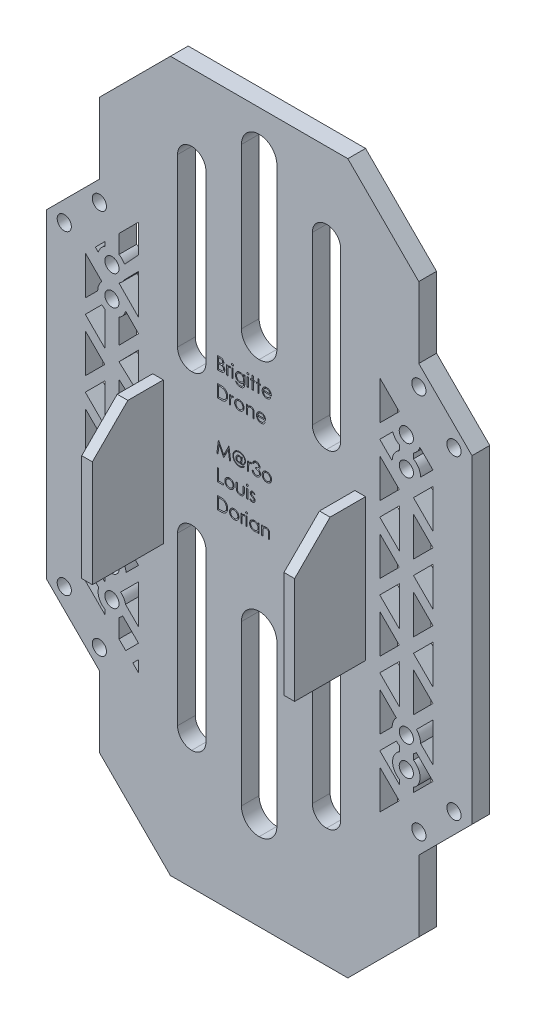
SolidWorks part; units mm, degrees
ref_plane "Plan de face" through (0, 0, 0) normal (0, 0, 1) x (1, 0, 0)
ref_plane "Plan de dessus" through (0, 0, 0) normal (0, 1, 0) x (1, 0, 0)
ref_plane "Plan de droite" through (0, 0, 0) normal (1, 0, 0) x (0, 0, -1)
sketch "Esquisse1" plane through (0, 0, 0) normal (0, 0, 1) x (1, 0, 0)
  line L0 (-41.0719, 30.2056) -> (78.9281, 30.2056)
  line L1 (78.9281, 30.2056) -> (78.9281, -89.7944)
  line L2 (78.9281, -89.7944) -> (-41.0719, -89.7944)
  line L3 (-41.0719, -89.7944) -> (-41.0719, 30.2056)
  dimension "D1" = 120
  dimension "D2" = 120
extrude "Boss.-Extru.2" add sketch "Esquisse1" along normal blind 5
sketch "Esquisse3" plane through (0, 0, 0) normal (0, 0, -1) x (-1, 0, 0)
sketch "Esquisse7" plane through (0, 0, 5) normal (0, 0, 1) x (1, 0, 0)
sketch "Esquisse9" plane through (0, 0, 5) normal (0, 0, 1) x (1, 0, 0)
  line L0 (-41.0719, -89.7944) -> (78.9281, -89.7944) construction
  line L1 (78.9281, -89.7944) -> (78.9281, 30.2056) construction
  circle A0 centre (-22.5719, -62.2944) radius 2
  circle A1 centre (-22.5719, 2.7056) radius 2
  circle A2 centre (60.4281, 2.7056) radius 2
  circle A3 centre (60.4281, -62.2944) radius 2
  dimension "D5" = 4
  dimension "D6" = 4
  dimension "D7" = 4
  dimension "D8" = 4
  dimension "D1" = 83
  dimension "D2" = 83
  dimension "D3" = 18.5
  dimension "D4" = 65
  dimension "D9" = 27.5
  dimension "D10" = 27.5
  dimension "D11" = 18.5
  dimension "D12" = 65
chamfer "Chanfrein5" distance 15 angle 45 1 edges at (78.9281, -89.7944, 2.5)
chamfer "Chanfrein6" distance 15 angle 45 1 edges at (78.9281, 30.2056, 2.5)
chamfer "Chanfrein7" distance 15 angle 45 1 edges at (-41.0719, 30.2056, 2.5)
chamfer "Chanfrein8" distance 15 angle 45 1 edges at (-41.0719, -89.7944, 2.5)
sketch "Esquisse21" plane through (0, -89.7944, 0) normal (0, -1, 0) x (-1, 0, 0)
  line L0 (26.0719, -5) -> (26.0719, 0)
  line L1 (26.0719, 0) -> (-63.9281, 0)
  line L2 (-63.9281, 0) -> (-63.9281, -5)
  line L3 (-63.9281, -5) -> (26.0719, -5)
extrude "Boss.-Extru.7" add sketch "Esquisse21" along normal blind 40
sketch "Esquisse22" plane through (0, 30.2056, 0) normal (0, 1, 0) x (1, 0, 0)
  line L0 (63.9281, -5) -> (63.9281, 0)
  line L1 (63.9281, 0) -> (-26.0719, 0) construction
  line L2 (63.9281, 0) -> (-26.0719, 0)
  line L3 (-26.0719, 0) -> (-26.0719, -5)
  line L4 (-26.0719, -5) -> (63.9281, -5)
extrude "Boss.-Extru.8" add sketch "Esquisse22" along normal blind 40
chamfer "Chanfrein23" distance 20 angle 45 4 edges at (-26.0719, -129.7944, 2.5) (63.9281, -129.7944, 2.5) (-26.0719, 70.2056, 2.5) (63.9281, 70.2056, 2.5)
sketch "Esquisse23" plane through (0, 0, 5) normal (0, 0, 1) x (1, 0, 0)
  line L0 (-41.0719, -74.7944) -> (-26.0719, -89.7944) construction
  line L2 (-35.9963, -74.2132) -> (-26.0968, -84.1127)
  line L3 (78.9281, 15.2056) -> (63.9281, 30.2056) construction
  line L4 (-35.9963, -74.2132) -> (-31.0465, -79.1629)
  line L5 (63.9281, -89.7944) -> (78.9281, -74.7944) construction
  line L6 (-31.0465, -79.1629) -> (-22.5612, -70.6777)
  line L9 (63.9532, -84.1124) -> (73.8527, -74.2129)
  line L10 (63.9532, -84.1124) -> (68.903, -79.1626)
  line L11 (68.903, -79.1626) -> (60.4177, -70.6774)
  line L14 (63.9532, 24.5237) -> (73.8527, 14.6242)
  line L15 (73.8527, 14.6242) -> (68.9029, 19.5739)
  line L16 (68.9029, 19.5739) -> (60.4176, 11.0886)
  line L17 (-35.9969, 14.6238) -> (-26.0974, 24.5232)
  line L18 (-26.0974, 24.5232) -> (-31.0472, 19.5735)
  line L19 (-31.0472, 19.5735) -> (-22.5619, 11.0882)
  line L27 (-26.0719, 30.2056) -> (-41.0719, 15.2056) construction
  line L31 (-41.0719, 15.2056) -> (-41.0719, -74.7944) construction
  circle A0 centre (-35.9963, -74.2132) radius 2
  circle A1 centre (-26.0968, -84.1127) radius 2
  circle A2 centre (-26.0974, 24.5232) radius 2
  circle A3 centre (-35.9969, 14.6238) radius 2
  circle A4 centre (63.9532, 24.5237) radius 2
  circle A5 centre (73.8527, 14.6242) radius 2
  circle A6 centre (63.9532, -84.1124) radius 2
  circle A7 centre (73.8527, -74.2129) radius 2
  circle A8 centre (-22.5612, -70.6777) radius 2
  circle A9 centre (60.4177, -70.6774) radius 2
  circle A10 centre (60.4176, 11.0886) radius 2
  circle A11 centre (-22.5619, 11.0882) radius 2
  dimension "D3" = 4
  dimension "D4" = 4
  dimension "D6" = 4
  dimension "D7" = 4
  dimension "D10" = 5.6818
  dimension "D15" = 4
  dimension "D16" = 4
  dimension "D19" = 14
  dimension "D23" = 4
  dimension "D24" = 4
  dimension "D26" = 4
  dimension "D27" = 4
  dimension "D28" = 4
  dimension "D30" = 4
  dimension "D1" = 4
  dimension "D2" = 4
  dimension "D5" = 14
  dimension "D8" = 14
  dimension "D9" = 4
  dimension "D11" = 4
  dimension "D12" = 5.075
  dimension "D13" = 14
  dimension "D14" = 4
  dimension "D17" = 4
  dimension "D18" = 5.682
  dimension "D20" = 4
  dimension "D21" = 5.682
  dimension "D22" = 4
  dimension "D25" = 12
  dimension "D29" = 12
  dimension "D31" = 12
  dimension "D32" = 12
extrude "Enlèv. mat.-Extru.1" cut sketch "Esquisse23" against normal blind 10 contours A0 | A1 | A6 | A7 | A5 | A4 | A10 | A11 | A2 | A3 | A8 | A9
sketch "Esquisse24" plane through (0, 0, 5) normal (0, 0, 1) x (1, 0, 0)
  line L0 (63.9281, -89.7944) -> (78.9281, -74.7944) construction
  circle A0 centre (63.5389, -84.5268) radius 2.5407
  circle A1 centre (73.4383, -74.6273) radius 2.5147
  dimension "D1" = 4
  dimension "D2" = 4
  dimension "D3" = 14
  dimension "D4" = 5.282
sketch "Sketch1" plane through (0, 0, 5) normal (0, 0, 1) x (1, 0, 0)
  line L1 (13.9281, -107.7944) -> (23.9281, -107.7944)
  line L2 (13.9281, -107.7944) -> (13.9281, -52.7944)
  line L3 (13.9281, -52.7944) -> (23.9281, -52.7944)
  line L4 (23.9281, -107.7944) -> (23.9281, -52.7944)
  line L6 (43.9281, -129.7944) -> (-6.0719, -129.7944) construction
  dimension "D1" = 10
  dimension "D2" = 55
  dimension "D3" = 40
  dimension "D4" = 22
extrude "Cut-Extrude2" cut sketch "Sketch1" against normal blind 5 contours L2 L1 L4 L3
fillet "Fillet2" radius 5 1 edges at (13.9281, -107.7944, 2.5)
fillet "Fillet3" radius 5 3 edges at (13.9281, -52.7944, 2.5) (23.9281, -52.7944, 2.5) (23.9281, -107.7944, 2.5)
sketch "Sketch2" plane through (0, 0, 5) normal (0, 0, 1) x (1, 0, 0)
  line L0 (23.9281, -102.7944) -> (23.9281, -57.7944) construction
  line L1 (41.9281, -96.2103) -> (33.9281, -96.2103)
  line L2 (41.9281, -96.2103) -> (41.9281, -41.2103)
  line L3 (41.9281, -41.2103) -> (33.9281, -41.2103)
  line L4 (33.9281, -96.2103) -> (33.9281, -41.2103)
  line L5 (13.9281, -102.7944) -> (13.9281, -57.7944) construction
  line L6 (3.9281, -96.2103) -> (-4.0719, -96.2103)
  line L7 (3.9281, -96.2103) -> (3.9281, -41.2103)
  line L8 (3.9281, -41.2103) -> (-4.0719, -41.2103)
  line L9 (-4.0719, -96.2103) -> (-4.0719, -41.2103)
  dimension "D1" = 10
  dimension "D2" = 10
  dimension "D3" = 8
  dimension "D4" = 8
  dimension "D5" = 55
  dimension "D6" = 55
sketch "Sketch3" plane through (0, 0, 5) normal (0, 0, 1) x (1, 0, 0)
  line L0 (78.9281, -74.7944) -> (78.9281, 15.2056) construction
  line L1 (23.9281, 63.6661) -> (13.9281, 63.6661)
  line L2 (23.9281, 63.6661) -> (23.9281, 8.6661)
  line L3 (23.9281, 8.6661) -> (13.9281, 8.6661)
  line L4 (13.9281, 63.6661) -> (13.9281, 8.6661)
  dimension "D1" = 10
  dimension "D2" = 55
  dimension "D3" = 55
extrude "Cut-Extrude4" cut sketch "Sketch3" against normal blind 5
fillet "Fillet11" radius 5 4 edges at (13.9281, 63.6661, 2.5) (23.9281, 63.6661, 2.5) (23.9281, 8.6661, 2.5) (13.9281, 8.6661, 2.5)
extrude "Cut-Extrude5" cut sketch "Sketch2" against normal blind 8
sketch "Sketch4" plane through (0, 0, 5) normal (0, 0, 1) x (1, 0, 0)
  line L0 (13.9281, 58.6661) -> (13.9281, 13.6661) construction
  line L1 (-4.0719, 51.2056) -> (3.9281, 51.2056)
  line L2 (-4.0719, 51.2056) -> (-4.0719, -3.7944)
  line L3 (-4.0719, -3.7944) -> (3.9281, -3.7944)
  line L4 (3.9281, 51.2056) -> (3.9281, -3.7944)
  line L5 (33.9281, 51.2056) -> (41.9281, 51.2056)
  line L6 (33.9281, 51.2056) -> (33.9281, -3.7944)
  line L7 (33.9281, -3.7944) -> (41.9281, -3.7944)
  line L8 (41.9281, 51.2056) -> (41.9281, -3.7944)
  line L9 (23.9281, 13.6661) -> (23.9281, 58.6661) construction
  line L10 (-6.0719, 70.2056) -> (43.9281, 70.2056) construction
  dimension "D1" = 8
  dimension "D2" = 55
  dimension "D3" = 55
  dimension "D4" = 8
  dimension "D5" = 10
  dimension "D6" = 10
  dimension "D7" = 19
  dimension "D8" = 19
extrude "Cut-Extrude6" cut sketch "Sketch4" against normal blind 8
fillet "Fillet12" radius 4 4 edges at (33.9281, 51.2056, 2.5) (41.9281, 51.2056, 2.5) (41.9281, -3.7944, 2.5) (33.9281, -3.7944, 2.5)
fillet "Fillet13" radius 4 4 edges at (-4.0719, -3.7944, 2.5) (3.9281, -3.7944, 2.5) (-4.0719, 51.2056, 2.5) (3.9281, 51.2056, 2.5)
fillet "Fillet14" radius 4 4 edges at (3.9281, -41.2103, 2.5) (-4.0719, -41.2103, 2.5) (-4.0719, -96.2103, 2.5) (3.9281, -96.2103, 2.5)
fillet "Fillet15" radius 4 4 edges at (41.9281, -96.2103, 2.5) (33.9281, -96.2103, 2.5) (33.9281, -41.2103, 2.5) (41.9281, -41.2103, 2.5)
sketch "Sketch5" plane through (0, 0, 5) normal (0, 0, 1) x (1, 0, 0)
  line L0 (-6.0719, 70.2056) -> (43.9281, 70.2056) construction
  line L1 (-11.0719, -9.7944) -> (-8.0719, -9.7944)
  line L2 (-11.0719, -9.7944) -> (-11.0719, -49.7944)
  line L3 (-11.0719, -49.7944) -> (-8.0719, -49.7944)
  line L4 (-8.0719, -9.7944) -> (-8.0719, -49.7944)
  line L5 (45.9281, -9.7944) -> (48.9281, -9.7944)
  line L6 (45.9281, -9.7944) -> (45.9281, -49.7944)
  line L7 (45.9281, -49.7944) -> (48.9281, -49.7944)
  line L8 (48.9281, -9.7944) -> (48.9281, -49.7944)
  line L9 (-41.0719, 15.2056) -> (-41.0719, -74.7944) construction
  dimension "D1" = 40
  dimension "D2" = 40
  dimension "D3" = 80
  dimension "D4" = 80
  dimension "D5" = 3
  dimension "D6" = 3
  dimension "D7" = 54
  dimension "D8" = 30
extrude "Boss-Extrude1" add sketch "Sketch5" along normal blind 20
chamfer "Chamfer1" distance 10 angle 45 1 edges at (47.4281, -9.7944, 25)
chamfer "Chamfer2" distance 10 angle 45 1 edges at (-9.5719, -9.7944, 25)
extrude "Cut-Extrude7" cut sketch "Esquisse9" against normal blind 10
sketch "Sketch6" plane through (0, 0, 5) normal (0, 0, 1) x (1, 0, 0)
  line L0 (-15.0719, -120.7944) -> (-15.0719, 61.2056)
  line L1 (-26.0719, -109.7944) -> (-6.0719, -129.7944) construction
  line L2 (-6.0719, 70.2056) -> (-26.0719, 50.2056) construction
  line L3 (-30.0719, -85.7944) -> (-30.0719, 26.2056)
  line L4 (-41.0719, -74.7944) -> (-26.0719, -89.7944) construction
  line L5 (-26.0719, 30.2056) -> (-41.0719, 15.2056) construction
  line L6 (-41.0719, 15.2056) -> (-41.0719, -74.7944) construction
  line L7 (-15.0719, 17.2056) -> (-20.5719, 11.2719)
  line L8 (-20.5719, -115.2944) -> (-20.5719, 55.7056)
  line L9 (-24.5719, -53.8095) -> (-24.5719, 126.1905)
  line L10 (-24.5719, -53.8095) -> (-24.5719, -111.2944)
  line L11 (-15.0719, -84.7944) -> (-30.0719, -69.7944)
  line L12 (-15.0719, 25.2056) -> (-30.0719, 10.2056)
  line L13 (-15.0719, 13.2056) -> (-20.5719, 7.5964)
  line L14 (-20.5719, 7.5964) -> (-15.0719, 1.9874)
  line L15 (-20.5719, 7.5964) -> (-15.0719, 7.5964)
  line L16 (-15.0719, -6.0126) -> (-20.5719, -11.6216)
  line L17 (-20.5719, 3.5964) -> (-20.2132, 3.2306)
  line L18 (-19.2957, 2.2949) -> (-15.0719, -2.0126)
  line L19 (-15.0719, -2.0126) -> (-20.5719, -7.6216)
  line L20 (-20.5719, -11.6216) -> (-15.0719, -16.6452)
  line L21 (-20.5719, -15.9374) -> (-15.0719, -20.6452)
  line L22 (-15.0719, -20.6452) -> (-20.5719, -26.0772)
  line L23 (-15.0719, -24.6452) -> (-20.5719, -30.0772)
  line L24 (-20.5719, -30.0772) -> (-15.0719, -35.5772)
  line L25 (-20.5719, -34.0772) -> (-15.0719, -39.5772)
  line L26 (-15.0719, -39.5772) -> (-20.5719, -45.0772)
  line L27 (-20.5719, -49.0772) -> (-15.0719, -43.5772)
  line L28 (-20.5719, -49.0772) -> (-15.0719, -54.5772)
  line L29 (-20.5719, -53.0772) -> (-15.0719, -58.5772)
  line L30 (-15.0719, -58.5772) -> (-20.5719, -58.5772)
  line L31 (-15.0719, -58.5772) -> (-20.5719, -64.0772)
  line L32 (-20.5719, -68.0772) -> (-15.0719, -68.0772)
  line L36 (-20.5719, -68.0772) -> (-15.0719, -73.5772)
  line L37 (-15.0719, -77.5772) -> (-20.5719, -77.5772)
  line L38 (-15.0719, -77.5772) -> (-20.5719, -83.0772)
  line L39 (-30.0719, 10.2056) -> (-24.5719, 4.7056)
  line L40 (-27.2435, 13.034) -> (-24.5719, 10.3625)
  line L41 (-24.5719, 4.7056) -> (-30.0719, 4.7056)
  line L43 (-24.5719, 4.7056) -> (-30.0719, -0.7944)
  line L45 (-30.0719, -65.7988) -> (-30.0719, -69.7944)
  line L46 (-30.0719, -4.7944) -> (-24.5719, -4.7944)
  line L47 (-30.0719, -4.7944) -> (-24.5719, -10.2944)
  line L48 (-30.0719, -8.7944) -> (-24.5719, -14.2944)
  line L49 (-24.5719, -14.2944) -> (-30.0719, -14.2944)
  line L50 (-24.5719, -14.2944) -> (-30.0719, -19.7944)
  line L51 (-24.5719, -18.2944) -> (-30.0719, -23.7944)
  line L52 (-30.0719, -23.7944) -> (-24.5719, -23.7944)
  line L53 (-30.0719, -23.7944) -> (-24.5719, -29.2944)
  line L54 (-30.0719, -27.7944) -> (-24.5719, -33.2944)
  line L55 (-24.5719, -33.2944) -> (-30.0719, -33.2944)
  line L56 (-24.5719, -33.2944) -> (-30.0719, -38.9521)
  line L57 (-24.5719, -37.2944) -> (-30.0719, -42.9521)
  line L58 (-30.0719, -42.9521) -> (-24.5719, -42.9521)
  line L59 (-30.0719, -42.9521) -> (-24.5719, -48.2988)
  line L60 (-30.0719, -46.9521) -> (-24.5719, -52.2988)
  line L61 (-24.5719, -52.2988) -> (-30.0719, -52.2988)
  line L62 (-24.5719, -52.2988) -> (-30.0719, -57.7988)
  line L63 (-24.5719, -56.2988) -> (-30.0719, -61.7988)
  line L64 (-30.0719, -61.7988) -> (-24.5719, -61.7988)
  line L66 (-30.0719, -65.7988) -> (-24.5719, -71.2988)
  line L67 (-30.0719, -4.7944) -> (-24.5719, 0.7056)
  line L68 (-24.5719, -75.2988) -> (-24.5697, -75.2966)
  line L70 (-30.0719, -69.7944) -> (-26.5697, -73.2966)
  line L71 (-20.5719, -68.0772) -> (-15.0719, -62.5772)
  line L72 (-20.5719, -72.0772) -> (-15.0719, -77.5772)
  line L73 (-15.0719, -81.5772) -> (-16.6805, -83.1858)
  line L74 (-30.0719, -61.7988) -> (-24.5719, -67.3403)
  circle A0 centre (-22.5719, -62.2944) radius 4
  circle A2 centre (-22.5612, -70.6777) radius 3.8963
  circle A3 centre (-22.5619, 11.0882) radius 4
  circle A4 centre (-22.5719, 2.7056) radius 4
  point P105 (0, 0)
  point P116 (0, 0)
  point P117 (-25.8481, -3.0448)
  dimension "D6" = 8
  dimension "D32" = 8
  dimension "D56" = 8
  dimension "D1" = 15
  dimension "D2" = 11
  dimension "D3" = 8
  dimension "D4" = 4
  dimension "D7" = 4
  dimension "D8" = 36
  dimension "D9" = 16
  dimension "D10" = 36
  dimension "D11" = 16
  dimension "D12" = 4
  dimension "D13" = 4
  dimension "D14" = 4
  dimension "D15" = 4
  dimension "D16" = 4
  dimension "D17" = 4
  dimension "D18" = 4
  dimension "D19" = 4
  dimension "D20" = 4
  dimension "D21" = 4
  dimension "D22" = 4
  dimension "D23" = 4
  dimension "D24" = 5.5
  dimension "D25" = 4
  dimension "D26" = 4
  dimension "D27" = 4
  dimension "D28" = 4
  dimension "D29" = 9.5
  dimension "D30" = 4
  dimension "D31" = 0
  dimension "D33" = 4
  dimension "D34" = 5.5
  dimension "D35" = 4
  dimension "D36" = 5.5
  dimension "D37" = 4
  dimension "D38" = 4
  dimension "D39" = 5.5
  dimension "D40" = 4
  dimension "D41" = 4
  dimension "D42" = 4
  dimension "D43" = 4
  dimension "D44" = 4
  dimension "D45" = 4
  dimension "D46" = 4
  dimension "D47" = 4
  dimension "D48" = 4
  dimension "D49" = 4
  dimension "D50" = 4
  dimension "D51" = 4
  dimension "D52" = 5.5
  dimension "D53" = 5.5
  dimension "D54" = 11
  dimension "D57" = 4
  dimension "D58" = 4
  dimension "D59" = 5.5
extrude "Cut-Extrude8" cut sketch "Sketch6" against normal blind 10 contours L0 L73 L11 | L38 L37 L8 L11 | A2 L8 L37 L72 | A2 L36 L0 L32 | A2 L32 L0 L71 | A0 L31 L30 L8 | L30 L29 L8 | L27 L28 L0 | L26 L25 L8 | L23 L24 L0 | L22 L21 L8 | L16 L20 L0 | A4 L8 L19 L18 | L15 L14 L0 | A3 L13 L15 L0 | A3 L7 L0 L12 L8 | A3 L9 L12 L40 | A4 L39 L3 L41 | A4 L41 L3 L43 | A4 L67 L46 L9 | L46 L47 L9 | L49 L48 L3 | L50 L49 L3 | L51 L52 L9 | L52 L53 L9 | L55 L54 L3 | L56 L55 L3 | L57 L58 L9 | L58 L59 L9 | L61 L60 L3 | L62 L61 L3 | A0 L10 L63 L64 | A0 L64 L74 L10 | A2 L66 L3 L11 L10 region at (-15.6081, -83.1858, 5) region at (-18.366, -78.8605, 5) region at (-18.6256, -75.9461, 5) region at (-16.7125, -69.9954, 5) region at (-16.8606, -66.2204, 5) region at (-27.868, -70.1846, 5) region at (-18.7386, -56.7438, 5) region at (-17.9347, -59.6603, 5) region at (-16.9053, -49.0772, 5) region at (-27.0269, -63.812, 5) region at (-26.776, -59.7222, 5) region at (-18.7386, -39.5772, 5) region at (-28.2386, -54.1321, 5) region at (-16.9053, -30.0999, 5) region at (-28.2386, -50.5165, 5) region at (-26.4053, -44.7343, 5) region at (-18.7386, -20.8866, 5) region at (-26.4053, -41.0662, 5) region at (-16.9053, -11.4265, 5) region at (-28.2386, -35.1803, 5) region at (-28.2386, -31.4611, 5) region at (-18.5306, -2.6196, 5) region at (-26.4053, -25.6277, 5) region at (-16.9053, 5.7267, 5) region at (-26.4053, -21.9611, 5) region at (-16.8706, 9.4797, 5) region at (-26.4727, -3.0866, 5) region at (-28.2386, -16.1277, 5) region at (-26.4053, -6.6277, 5) region at (-28.2386, -12.4611, 5) region at (-17.7026, 18.6721, 5) region at (-28.538, 2.7336, 5) region at (-28.3642, 6.6064, 5) region at (-25.8309, 13.8848, 5)
sketch "Sketch9" plane through (0, 0, 5) normal (0, 0, 1) x (1, 0, 0)
  line L0 (78.9281, -74.7944) -> (78.9281, 15.2056) construction
  line L1 (58.4281, -60.2944) -> (52.9281, -60.2944)
  line L2 (43.9281, -129.7944) -> (63.9281, -109.7944) construction
  line L3 (62.4281, -111.2944) -> (62.4281, 51.7056)
  line L4 (63.9281, 50.2056) -> (43.9281, 70.2056) construction
  line L5 (58.4281, -115.2944) -> (58.4281, 55.7056)
  line L6 (67.9281, -85.7944) -> (67.9281, 26.2056)
  line L7 (63.9281, -89.7944) -> (78.9281, -74.7944) construction
  line L8 (78.9281, 15.2056) -> (63.9281, 30.2056) construction
  line L9 (52.9281, -120.7944) -> (52.9281, 61.2056)
  line L10 (52.9281, -120.7944) -> (52.9281, -84.7944)
  line L11 (67.9281, -85.7944) -> (67.9281, -69.7944)
  line L12 (52.9281, -84.7944) -> (67.9281, -69.7944)
  line L13 (52.9281, -79.2944) -> (58.4281, -79.2944)
  line L14 (58.4281, -79.2944) -> (52.9281, -73.7944)
  line L15 (52.9281, -69.7944) -> (58.4281, -75.2944)
  line L16 (52.9281, -69.7944) -> (58.4281, -69.7944)
  line L17 (52.9281, -69.7944) -> (58.4281, -64.2944)
  line L18 (52.9281, -65.7944) -> (58.4281, -60.2944)
  line L19 (58.4281, -60.2944) -> (52.9281, -54.7944)
  line L20 (52.9281, -50.7944) -> (58.4281, -56.2944)
  line L21 (52.9281, -50.7944) -> (58.4281, -50.7944)
  line L22 (52.9281, -50.7944) -> (58.4281, -45.2944)
  line L23 (52.9281, -46.7944) -> (58.4281, -41.2944)
  line L24 (58.4281, -41.2944) -> (52.9281, -41.2944)
  line L25 (58.4281, -41.2944) -> (52.9281, -35.7944)
  line L26 (52.9281, -31.7944) -> (58.4281, -37.2944)
  line L27 (52.9281, -31.7944) -> (58.4281, -31.7944)
  line L28 (52.9281, -31.7944) -> (58.4281, -26.2944)
  line L29 (52.9281, -27.7944) -> (58.4281, -22.2944)
  line L30 (58.4281, -22.2944) -> (52.9281, -22.2944)
  line L31 (58.4281, -22.2944) -> (52.9281, -16.7944)
  line L32 (52.9281, -12.7944) -> (58.4281, -18.2944)
  line L33 (52.9281, -12.7944) -> (58.4281, -12.7944)
  line L34 (52.9281, -12.7944) -> (58.4281, -7.2944)
  line L35 (52.9281, -8.7944) -> (58.4281, -3.2944)
  line L36 (58.4281, -3.2944) -> (52.9281, -3.2944)
  line L37 (58.4281, -3.2944) -> (52.9281, 2.2056)
  line L38 (58.4281, 0.7056) -> (52.9281, 6.2056)
  line L39 (52.9281, 6.2056) -> (58.4281, 6.2056)
  line L40 (52.9281, 6.2056) -> (58.4281, 11.7056)
  line L41 (52.9281, 10.2056) -> (58.4281, 15.7056)
  line L42 (52.9281, 61.2056) -> (52.9281, 25.2056)
  line L43 (67.9281, 26.2056) -> (67.9281, 10.2056)
  line L44 (52.9281, 25.2056) -> (67.9281, 10.2056)
  line L45 (58.4281, 15.7056) -> (52.9281, 15.7056)
  line L46 (58.4281, 15.7056) -> (52.9281, 21.2056)
  line L47 (58.4281, 19.7056) -> (52.9281, 25.2056)
  line L48 (67.9281, -69.7944) -> (62.4281, -69.7944)
  line L49 (67.9281, -69.7944) -> (62.4281, -64.2944)
  line L50 (67.9281, -65.7944) -> (62.4281, -60.2944)
  line L51 (62.4281, -60.2944) -> (67.9281, -60.2944)
  line L52 (62.4281, -60.2944) -> (67.9281, -54.7944)
  line L53 (62.4281, -56.2944) -> (67.9281, -50.7944)
  line L54 (67.9281, -50.7944) -> (62.4281, -50.7944)
  line L55 (67.9281, -50.7944) -> (62.4281, -45.2944)
  line L56 (62.4281, -41.2944) -> (67.9281, -46.7944)
  line L57 (62.4281, -41.2944) -> (67.9281, -41.2944)
  line L58 (62.4281, -41.2944) -> (67.9281, -35.7944)
  line L59 (62.4281, -37.2944) -> (67.9281, -31.7944)
  line L60 (67.9281, -31.7944) -> (62.4281, -31.7944)
  line L61 (67.9281, -31.7944) -> (62.4281, -26.2944)
  line L62 (67.9281, -27.7944) -> (62.4281, -22.2944)
  line L63 (62.4281, -22.2944) -> (67.9281, -22.2944)
  line L64 (62.4281, -22.2944) -> (67.9281, -16.7944)
  line L65 (62.4281, -18.2944) -> (67.9281, -12.7944)
  line L66 (67.9281, -12.7944) -> (62.4281, -12.7944)
  line L67 (67.9281, -12.7944) -> (62.4281, -7.2944)
  line L68 (67.9281, -8.7944) -> (62.4281, -3.2944)
  line L69 (62.4281, -3.2944) -> (67.9281, -3.2944)
  line L70 (62.4281, -3.2944) -> (67.9281, 2.2056)
  line L71 (62.4281, 0.7056) -> (67.9281, 6.2056)
  line L72 (67.9281, 6.2056) -> (62.4281, 6.2056)
  line L73 (67.9281, 6.2056) -> (62.4281, 11.7056)
  circle A0 centre (60.4281, -62.2944) radius 4
  circle A1 centre (60.4281, 2.7056) radius 4
  circle A2 centre (60.4176, 11.0886) radius 4
  circle A3 centre (60.4177, -70.6774) radius 3.8769
  dimension "D12" = 8
  dimension "D13" = 8
  dimension "D73" = 8
  dimension "D1" = 11
  dimension "D2" = 4
  dimension "D3" = 5.5
  dimension "D4" = 5.5
  dimension "D5" = 36
  dimension "D6" = 16
  dimension "D7" = 5.5
  dimension "D8" = 4
  dimension "D9" = 5.5
  dimension "D10" = 4
  dimension "D11" = 5.5
  dimension "D14" = 4
  dimension "D15" = 4
  dimension "D16" = 5.5
  dimension "D17" = 5.5
  dimension "D18" = 5.5
  dimension "D19" = 4
  dimension "D20" = 4
  dimension "D21" = 5.5
  dimension "D22" = 5.5
  dimension "D23" = 4
  dimension "D24" = 4
  dimension "D25" = 5.5
  dimension "D26" = 5.5
  dimension "D27" = 4
  dimension "D28" = 4
  dimension "D29" = 5.5
  dimension "D30" = 4
  dimension "D31" = 4
  dimension "D32" = 5.5
  dimension "D33" = 4
  dimension "D34" = 4
  dimension "D35" = 5.5
  dimension "D36" = 4
  dimension "D37" = 4
  dimension "D38" = 5.5
  dimension "D39" = 4
  dimension "D40" = 4
  dimension "D41" = 5.5
  dimension "D42" = 4
  dimension "D43" = 4
  dimension "D44" = 36
  dimension "D45" = 5.5
  dimension "D46" = 4
  dimension "D47" = 4
  dimension "D48" = 5.5
  dimension "D49" = 4
  dimension "D50" = 4
  dimension "D51" = 5.5
  dimension "D52" = 4
  dimension "D53" = 4
  dimension "D54" = 5.5
  dimension "D55" = 4
  dimension "D56" = 4
  dimension "D57" = 4
  dimension "D58" = 4
  dimension "D59" = 4
  dimension "D60" = 5.5
  dimension "D61" = 4
  dimension "D62" = 5.5
  dimension "D63" = 4
  dimension "D64" = 4
  dimension "D65" = 5.5
  dimension "D66" = 4
  dimension "D67" = 4
  dimension "D68" = 5.5
  dimension "D69" = 4
  dimension "D70" = 4
  dimension "D71" = 4
  dimension "D72" = 5.5
extrude "Cut-Extrude10" cut sketch "Sketch9" against normal blind 10 contours L13 L14 L9 | L16 L15 L5 | A0 L17 L16 L5 | L9 L18 L1 | L1 L19 L9 | L22 L21 L5 | L21 L20 L5 | L23 L24 L9 | L24 L25 L9 | L27 L26 L5 | L28 L27 L5 | L30 L31 L9 | L29 L30 L9 | L33 L32 L5 | L34 L33 L5 | A1 L37 L9 L36 | L35 L36 L9 | L40 L39 L5 | A1 L5 L39 L38 | L41 L45 L9 | L45 L46 L9 | L13 L9 L12 | L72 L73 L3 | A1 L71 L72 L3 | A1 L70 L69 L6 | L69 L68 L6 | L66 L67 L3 | L65 L66 L3 | L64 L63 L6 | L63 L62 L6 | L60 L61 L3 | L59 L60 L3 | L58 L57 L6 | L57 L56 L6 | L54 L55 L3 | L53 L54 L3 | L52 L51 L6 | L51 L50 L6 | A0 L3 L48 L49 | L12 L48 L3 region at (54.462, -62.2664, 5) region at (54.6358, -58.3936, 5) region at (56.2348, -67.8978, 5) region at (56.5947, -52.6277, 5) region at (64.6168, -67.9007, 5) region at (55.9098, -71.7064, 5) region at (56.5947, -48.9611, 5) region at (64.2614, -52.6277, 5) region at (66.2203, -58.3936, 5) region at (54.7614, -77.4611, 5) region at (54.7614, -43.1277, 5) region at (66.3941, -62.2664, 5) region at (64.2614, -48.9611, 5) region at (64.936, -71.7082, 5) region at (54.7614, -81.1277, 5) region at (54.7614, -39.4611, 5) region at (66.0947, -43.1277, 5) region at (56.5947, -33.6277, 5) region at (66.0947, -39.4611, 5) region at (56.5947, -29.9611, 5) region at (64.2614, -33.6277, 5) region at (54.7614, -24.1277, 5) region at (64.2614, -29.9611, 5) region at (54.7614, -20.4611, 5) region at (66.0947, -24.1277, 5) region at (56.5947, -14.6277, 5) region at (66.0947, -20.4611, 5) region at (56.5947, -10.9611, 5) region at (64.2614, -14.6277, 5) region at (54.7614, -5.1277, 5) region at (64.2614, -10.9611, 5) region at (54.7614, -1.4611, 5) region at (66.0947, -5.1277, 5) region at (66.0947, -1.4611, 5) region at (55.7043, 5.126, 5) region at (56.1333, 7.4254, 5) region at (65.1518, 5.126, 5) region at (54.7614, 13.8723, 5) region at (64.7178, 7.4312, 5) region at (54.7614, 17.5389, 5)
sketch "Sketch10" plane through (0, 0, 5) normal (0, 0, 1) x (1, 0, 0)
  text T0 "Brigitte\r\nDrone\r\n\r\nM@r3o\r\nLouis\r\nDorian"
extrude "Cut-Extrude11" cut sketch "Sketch10" against normal blind 2
